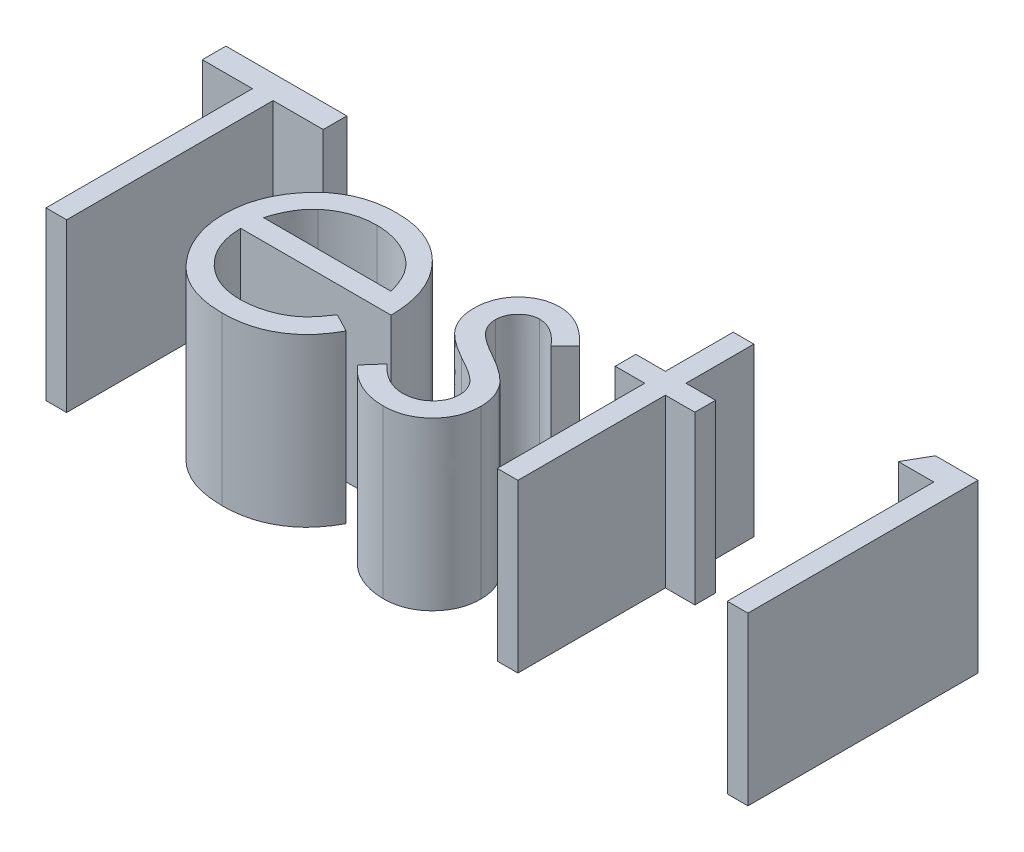
SolidWorks part; units mm, degrees
ref_plane "Front Plane" through (0, 0, 0) normal (0, 0, 1) x (1, 0, 0)
ref_plane "Top Plane" through (0, 0, 0) normal (0, 1, 0) x (1, 0, 0)
ref_plane "Right Plane" through (0, 0, 0) normal (1, 0, 0) x (0, 0, -1)
sketch "Sketch2" plane through (0, 0, 0) normal (0, 1, 0) x (1, 0, 0)
  line L0 (0, 0) -> (43.4315, 0) construction
  text T0 "Test 1"
  point P2 (5.1868, 2.31)
  point P4 (1.5032, 0)
  point P5 (-4.8699, 0)
extrude "Boss-Extrude1" add sketch "Sketch2" along normal blind 2.54
